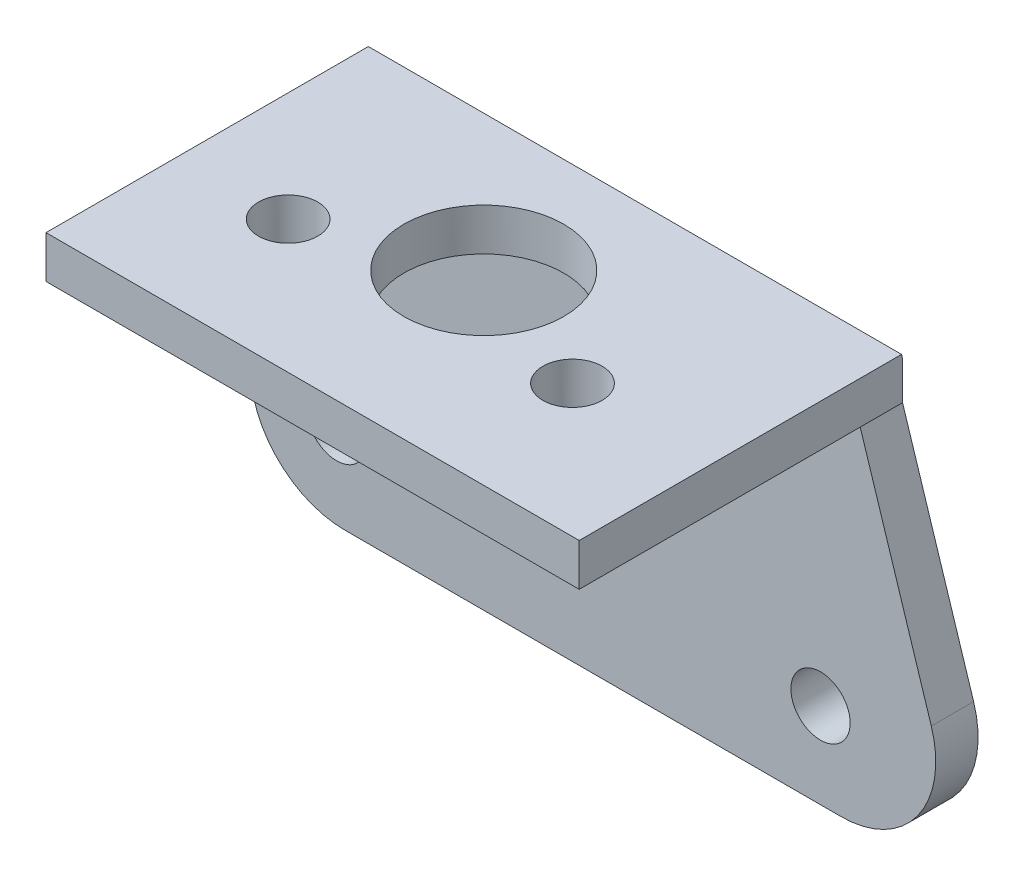
SolidWorks part; units mm, degrees
ref_plane "Front Plane" through (0, 0, 0) normal (0, 0, 1) x (1, 0, 0)
ref_plane "Top Plane" through (0, 0, 0) normal (0, 1, 0) x (1, 0, 0)
ref_plane "Right Plane" through (0, 0, 0) normal (1, 0, 0) x (0, 0, -1)
ref_plane "Plane1" through (0, 0, 5) normal (0, 0, 1) x (1, 0, 0)
sketch "Sketch1" plane through (0, 0, 5) normal (0, 0, 1) x (1, 0, 0)
  line L0 (-21.23, 0) -> (-27.3364, -18.8061)
  line L1 (-19.7275, -29.2768) -> (22.1459, -29.2768)
  line L2 (29.7692, -18.8507) -> (23.77, 0)
  line L3 (23.77, 0) -> (23.77, 5)
  line L4 (23.77, 5) -> (-21.23, 5)
  line L5 (-21.23, 5) -> (-21.23, 0)
  arc A0 (-27.3364, -18.8061) -> (-19.7275, -29.2768) centre (-19.7275, -21.2768) ccw
  arc A1 (22.1459, -29.2768) -> (29.7692, -18.8507) centre (22.1459, -21.2768) ccw
extrude "Boss-Extrude1" add sketch "Sketch1" against normal blind 3.5719
sketch "Sketch2" plane through (0, 0, 5) normal (0, 0, 1) x (1, 0, 0)
  line L0 (23.77, 0) -> (-21.23, 0)
  line L1 (-21.23, 0) -> (-21.23, 3.5719)
  line L2 (-21.23, 3.5719) -> (23.77, 3.5719)
  line L3 (23.77, 3.5719) -> (23.77, 0)
  dimension "D1" = 3.5719
extrude "Boss-Extrude2" add sketch "Sketch2" along normal blind 23.715
hole_wizard "Ø5.0 (5) Diameter Hole1" positions "Sketch4" profile "Sketch3" hole size "Ø5.0" standard "ANSI Metric"
sketch "Sketch4" plane through (0, 0, 1.4281) normal (0, 0, -1) x (-1, 0, 0)
  point P0 (-20.42, -22.057)
  point P1 (20.42, -22.057)
sketch "Sketch3" plane through (20.42, -22.057, 1.4281) normal (1, 0, 0) x (0, 1, 0)
  line L0 (0, 0) -> (0, 27.2868)
  line L1 (0, 27.2868) -> (2.5, 27.2868)
  line L2 (2.5, 27.2868) -> (2.5, 0)
  line L5 (2.5, 0) -> (0, 0)
  line L11 (0, -6.35) -> (0, 107.95) construction
  dimension "Thru Hole Dia." = 5
  dimension "Thru Hole Depth" = 27.2868
fillet "Fillet1" radius 2 1 edges at (1.27, 5, 1.4281) tangent propagation no
fillet "Fillet2" [suppressed] radius 8 tangent propagation no
hole_wizard "Ø13.5 (13.5) Diameter Hole1" positions "Sketch6" profile "Sketch5" hole size "Ø13.5" standard "ANSI Metric"
sketch "Sketch6" plane through (0, 5, 0) normal (0, 1, 0) x (1, 0, 0)
  line L0 (-55, -5) -> (55, -5) construction
  point P0 (0, -13)
  dimension "D1" = 8
sketch "Sketch5" plane through (0, 5, 13) normal (1, 0, 0) x (0, 0, 1)
  line L0 (0, 0) -> (0, 34.2768)
  line L1 (0, 34.2768) -> (6.75, 34.2768)
  line L2 (6.75, 34.2768) -> (6.75, 0)
  line L5 (6.75, 0) -> (0, 0)
  line L11 (0, -6.35) -> (0, 107.95) construction
  dimension "Thru Hole Dia." = 13.5
  dimension "Thru Hole Depth" = 34.2768
hole_wizard "Ø5.0 (5) Diameter Hole2" positions "Sketch8" profile "Sketch7" hole size "Ø5.0" standard "ANSI Metric"
sketch "Sketch8" plane through (0, 5, 0) normal (0, 1, 0) x (1, 0, 0)
  line L0 (-55, -5) -> (55, -5) construction
  point P0 (-12, -17.51)
  point P1 (12, -17.51)
  point P12 (9, -17.51)
  dimension "D1" = 12.51
  dimension "D2" = 12.51
  dimension "D3" = 12
  dimension "D4" = 24
sketch "Sketch7" plane through (-12, 5, 17.51) normal (1, 0, 0) x (0, 0, 1)
  line L0 (0, 0) -> (0, 34.2768)
  line L1 (0, 34.2768) -> (2.5, 34.2768)
  line L2 (2.5, 34.2768) -> (2.5, 0)
  line L5 (2.5, 0) -> (0, 0)
  line L11 (0, -6.35) -> (0, 107.95) construction
  dimension "Thru Hole Dia." = 5
  dimension "Thru Hole Depth" = 34.2768
sketch "Sketch9" plane through (0, 0, 5) normal (0, 0, 1) x (1, 0, 0)
  line L1 (-21.23, 3.5719) -> (23.77, 3.5719)
  line L2 (-21.23, 3.5719) -> (-21.23, 5)
  line L3 (-21.23, 5) -> (23.77, 5)
  line L4 (23.77, 3.5719) -> (23.77, 5)
extrude "Cut-Extrude1" cut sketch "Sketch9" against normal blind 10
